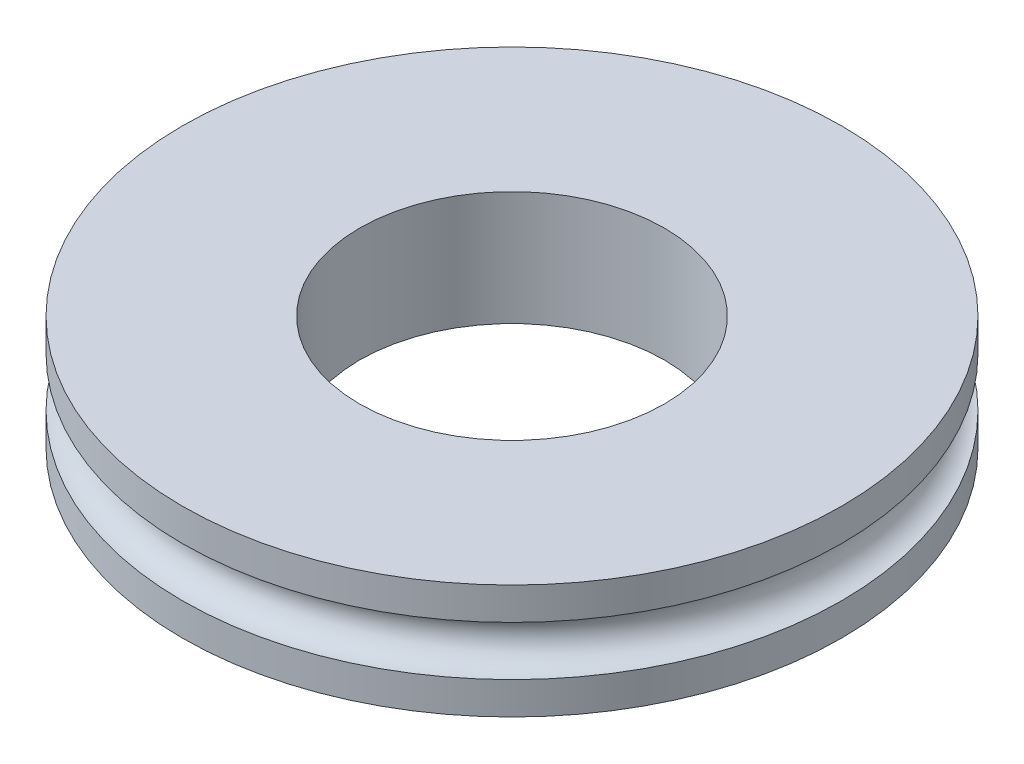
SolidWorks part; units mm, degrees
ref_plane "Front Plane" through (0, 0, 0) normal (0, 0, 1) x (1, 0, 0)
ref_plane "Top Plane" through (0, 0, 0) normal (0, 1, 0) x (1, 0, 0)
ref_plane "Right Plane" through (0, 0, 0) normal (1, 0, 0) x (0, 0, -1)
sketch "Sketch1" plane through (0, 0, 0) normal (0, 0, 1) x (1, 0, 0)
  line L0 (0, -1.5) -> (0, 1.5) construction
  line L1 (0, 1.5) -> (8.65, 1.5) construction
  line L2 (8.65, 1.5) -> (8.65, -1.5) construction
  line L3 (8.65, -1.5) -> (0, -1.5) construction
  line L4 (4, 1.5) -> (4, -1.5)
  line L5 (4, 0.65) -> (8.65, 0.65) construction
  line L6 (4, -0.65) -> (8.65, -0.65) construction
  line L7 (8.65, -0.65) -> (8.65, -1.5)
  line L8 (8.65, -1.5) -> (4, -1.5)
  line L9 (4, 1.5) -> (8.65, 1.5)
  line L10 (8.65, 1.5) -> (8.65, 0.65)
  line L11 (4, 0) -> (8, 0) construction
  arc A0 (8.65, 0.65) -> (8.65, -0.65) centre (8.65, 0) ccw
  point P4 (0, 0)
  dimension "D2" = 8
  dimension "D3" = 1.3
  dimension "D1" = 4
  dimension "D4" = 3
revolve "Revolve1" add sketch "Sketch1" angle 360 about L0
